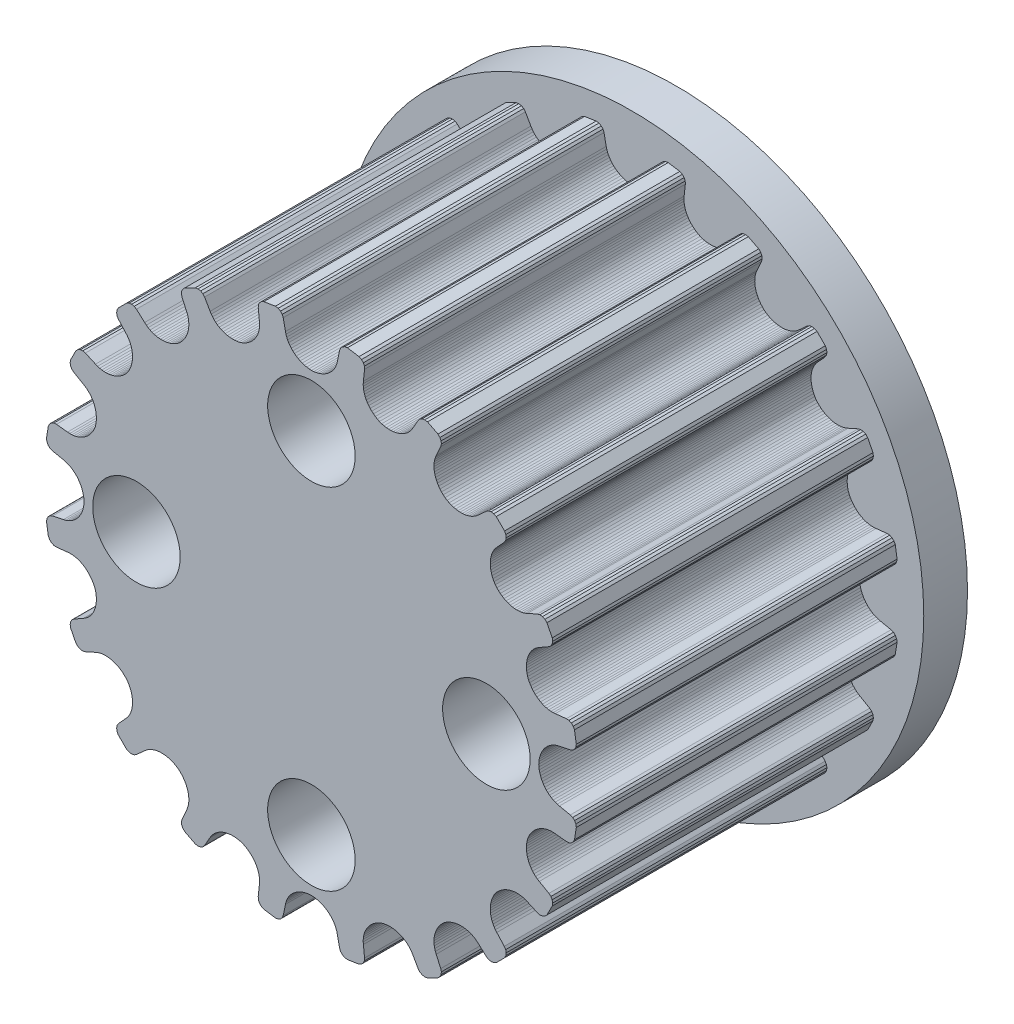
SolidWorks part; units mm, degrees
ref_plane "Front Plane" through (0, 0, 0) normal (0, 0, 1) x (1, 0, 0)
ref_plane "Top Plane" through (0, 0, 0) normal (0, 1, 0) x (1, 0, 0)
ref_plane "Right Plane" through (0, 0, 0) normal (1, 0, 0) x (0, 0, -1)
sketch "Model" plane through (0, 0, 0) normal (0, 0, 1) x (1, 0, 0)
  line L0 (-1.2351, -9.0847) -> (-1.1407, -9.0693)
  line L1 (-1.1407, -9.0693) -> (-1.0601, -9.0262)
  line L2 (-1.0601, -9.0262) -> (-1.0001, -8.9608)
  line L3 (-1.0001, -8.9608) -> (-0.9675, -8.878)
  line L4 (-0.9675, -8.878) -> (-0.8892, -8.5051)
  line L5 (-0.8892, -8.5051) -> (-0.8714, -8.4315)
  line L6 (-0.8714, -8.4315) -> (-0.847, -8.3606)
  line L7 (-0.847, -8.3606) -> (-0.8163, -8.2926)
  line L8 (-0.8163, -8.2926) -> (-0.7798, -8.2278)
  line L9 (-0.7798, -8.2278) -> (-0.7377, -8.1665)
  line L10 (-0.7377, -8.1665) -> (-0.6904, -8.109)
  line L11 (-0.6904, -8.109) -> (-0.6382, -8.0554)
  line L12 (-0.6382, -8.0554) -> (-0.5813, -8.0061)
  line L13 (-0.5813, -8.0061) -> (-0.5202, -7.9613)
  line L14 (-0.5202, -7.9613) -> (-0.4551, -7.9212)
  line L15 (-0.4551, -7.9212) -> (-0.3865, -7.8862)
  line L16 (-0.3865, -7.8862) -> (-0.3145, -7.8565)
  line L17 (-0.3145, -7.8565) -> (-0.2395, -7.8323)
  line L18 (-0.2395, -7.8323) -> (-0.162, -7.8139)
  line L19 (-0.162, -7.8139) -> (-0.0821, -7.8016)
  line L20 (-0.0821, -7.8016) -> (-0.0002, -7.7957)
  line L21 (-0.0002, -7.7957) -> (0.0817, -7.8016)
  line L22 (0.0817, -7.8016) -> (0.1616, -7.8138)
  line L23 (0.1616, -7.8138) -> (0.2392, -7.8322)
  line L24 (0.2392, -7.8322) -> (0.3142, -7.8563)
  line L25 (0.3142, -7.8563) -> (0.3861, -7.886)
  line L26 (0.3861, -7.886) -> (0.4548, -7.9211)
  line L27 (0.4548, -7.9211) -> (0.5199, -7.9611)
  line L28 (0.5199, -7.9611) -> (0.5811, -8.0059)
  line L29 (0.5811, -8.0059) -> (0.6379, -8.0553)
  line L30 (0.6379, -8.0553) -> (0.6902, -8.1089)
  line L31 (0.6902, -8.1089) -> (0.7375, -8.1665)
  line L32 (0.7375, -8.1665) -> (0.7796, -8.2278)
  line L33 (0.7796, -8.2278) -> (0.8161, -8.2926)
  line L34 (0.8161, -8.2926) -> (0.8467, -8.3606)
  line L35 (0.8467, -8.3606) -> (0.871, -8.4315)
  line L36 (0.871, -8.4315) -> (0.8888, -8.5051)
  line L37 (0.8888, -8.5051) -> (0.9668, -8.878)
  line L38 (0.9668, -8.878) -> (1, -8.9608)
  line L39 (1, -8.9608) -> (1.0602, -9.0262)
  line L40 (1.0602, -9.0262) -> (1.1407, -9.0693)
  line L41 (1.1407, -9.0693) -> (1.2351, -9.0847)
  line L42 (1.2351, -9.0847) -> (1.6327, -9.0218)
  line L43 (1.6327, -9.0218) -> (1.7177, -8.9779)
  line L44 (1.7177, -8.9779) -> (1.781, -8.912)
  line L45 (1.781, -8.912) -> (1.8178, -8.8313)
  line L46 (1.8178, -8.8313) -> (1.8233, -8.7425)
  line L47 (1.8233, -8.7425) -> (1.7825, -8.3636)
  line L48 (1.7825, -8.3636) -> (1.7768, -8.2881)
  line L49 (1.7768, -8.2881) -> (1.778, -8.2131)
  line L50 (1.778, -8.2131) -> (1.7862, -8.139)
  line L51 (1.7862, -8.139) -> (1.8009, -8.0661)
  line L52 (1.8009, -8.0661) -> (1.822, -7.9948)
  line L53 (1.822, -7.9948) -> (1.8492, -7.9254)
  line L54 (1.8492, -7.9254) -> (1.8823, -7.8583)
  line L55 (1.8823, -7.8583) -> (1.9212, -7.7939)
  line L56 (1.9212, -7.7939) -> (1.9654, -7.7324)
  line L57 (1.9654, -7.7324) -> (2.0149, -7.6742)
  line L58 (2.0149, -7.6742) -> (2.0694, -7.6196)
  line L59 (2.0694, -7.6196) -> (2.1287, -7.5691)
  line L60 (2.1287, -7.5691) -> (2.1925, -7.523)
  line L61 (2.1925, -7.523) -> (2.2606, -7.4816)
  line L62 (2.2606, -7.4816) -> (2.3328, -7.4452)
  line L63 (2.3328, -7.4452) -> (2.4088, -7.4142)
  line L64 (2.4088, -7.4142) -> (2.4885, -7.3945)
  line L65 (2.4885, -7.3945) -> (2.5683, -7.3815)
  line L66 (2.5683, -7.3815) -> (2.6478, -7.3749)
  line L67 (2.6478, -7.3749) -> (2.7265, -7.3747)
  line L68 (2.7265, -7.3747) -> (2.8042, -7.3808)
  line L69 (2.8042, -7.3808) -> (2.8803, -7.3928)
  line L70 (2.8803, -7.3928) -> (2.9546, -7.4108)
  line L71 (2.9546, -7.4108) -> (3.0266, -7.4345)
  line L72 (3.0266, -7.4345) -> (3.0959, -7.4639)
  line L73 (3.0959, -7.4639) -> (3.1622, -7.4987)
  line L74 (3.1622, -7.4987) -> (3.225, -7.5389)
  line L75 (3.225, -7.5389) -> (3.284, -7.5842)
  line L76 (3.284, -7.5842) -> (3.3387, -7.6345)
  line L77 (3.3387, -7.6345) -> (3.3888, -7.6897)
  line L78 (3.3888, -7.6897) -> (3.4339, -7.7497)
  line L79 (3.4339, -7.7497) -> (3.4736, -7.8142)
  line L80 (3.4736, -7.8142) -> (3.6629, -8.1447)
  line L81 (3.6629, -8.1447) -> (3.7201, -8.2132)
  line L82 (3.7201, -8.2132) -> (3.7975, -8.2568)
  line L83 (3.7975, -8.2568) -> (3.8875, -8.2729)
  line L84 (3.8875, -8.2729) -> (3.982, -8.2584)
  line L85 (3.982, -8.2584) -> (4.3407, -8.0757)
  line L86 (4.3407, -8.0757) -> (4.4079, -8.0077)
  line L87 (4.4079, -8.0077) -> (4.4478, -7.9255)
  line L88 (4.4478, -7.9255) -> (4.4579, -7.8373)
  line L89 (4.4579, -7.8373) -> (4.4356, -7.7512)
  line L90 (4.4356, -7.7512) -> (4.2798, -7.4035)
  line L91 (4.2798, -7.4035) -> (4.251, -7.3334)
  line L92 (4.251, -7.3334) -> (4.229, -7.2617)
  line L93 (4.229, -7.2617) -> (4.2138, -7.1887)
  line L94 (4.2138, -7.1887) -> (4.2053, -7.1148)
  line L95 (4.2053, -7.1148) -> (4.2033, -7.0405)
  line L96 (4.2033, -7.0405) -> (4.2078, -6.9661)
  line L97 (4.2078, -6.9661) -> (4.2186, -6.8921)
  line L98 (4.2186, -6.8921) -> (4.2356, -6.8187)
  line L99 (4.2356, -6.8187) -> (4.2587, -6.7466)
  line L100 (4.2587, -6.7466) -> (4.2878, -6.6759)
  line L101 (4.2878, -6.6759) -> (4.3227, -6.6072)
  line L102 (4.3227, -6.6072) -> (4.3635, -6.5409)
  line L103 (4.3635, -6.5409) -> (4.4099, -6.4773)
  line L104 (4.4099, -6.4773) -> (4.4619, -6.4168)
  line L105 (4.4619, -6.4168) -> (4.5193, -6.3599)
  line L106 (4.5193, -6.3599) -> (4.582, -6.307)
  line L107 (4.582, -6.307) -> (4.6518, -6.2636)
  line L108 (4.6518, -6.2636) -> (4.7236, -6.2265)
  line L109 (4.7236, -6.2265) -> (4.7972, -6.1958)
  line L110 (4.7972, -6.1958) -> (4.872, -6.1713)
  line L111 (4.872, -6.1713) -> (4.9477, -6.153)
  line L112 (4.9477, -6.153) -> (5.0239, -6.1409)
  line L113 (5.0239, -6.1409) -> (5.1001, -6.1351)
  line L114 (5.1001, -6.1351) -> (5.1759, -6.1354)
  line L115 (5.1759, -6.1354) -> (5.2509, -6.1419)
  line L116 (5.2509, -6.1419) -> (5.3247, -6.1545)
  line L117 (5.3247, -6.1545) -> (5.3968, -6.1733)
  line L118 (5.3968, -6.1733) -> (5.4669, -6.1982)
  line L119 (5.4669, -6.1982) -> (5.5345, -6.2291)
  line L120 (5.5345, -6.2291) -> (5.5992, -6.2662)
  line L121 (5.5992, -6.2662) -> (5.6606, -6.3092)
  line L122 (5.6606, -6.3092) -> (5.7183, -6.3583)
  line L123 (5.7183, -6.3583) -> (6.0005, -6.6142)
  line L124 (6.0005, -6.6142) -> (6.076, -6.6616)
  line L125 (6.076, -6.6616) -> (6.1632, -6.6792)
  line L126 (6.1632, -6.6792) -> (6.2536, -6.6667)
  line L127 (6.2536, -6.6667) -> (6.3391, -6.6238)
  line L128 (6.3391, -6.6238) -> (6.6238, -6.3391)
  line L129 (6.6238, -6.3391) -> (6.6667, -6.2536)
  line L130 (6.6667, -6.2536) -> (6.6792, -6.1631)
  line L131 (6.6792, -6.1631) -> (6.6615, -6.0761)
  line L132 (6.6615, -6.0761) -> (6.6138, -6.0011)
  line L133 (6.6138, -6.0011) -> (6.3581, -5.7186)
  line L134 (6.3581, -5.7186) -> (6.3091, -5.6609)
  line L135 (6.3091, -5.6609) -> (6.266, -5.5994)
  line L136 (6.266, -5.5994) -> (6.229, -5.5347)
  line L137 (6.229, -5.5347) -> (6.1981, -5.4671)
  line L138 (6.1981, -5.4671) -> (6.1732, -5.397)
  line L139 (6.1732, -5.397) -> (6.1545, -5.3249)
  line L140 (6.1545, -5.3249) -> (6.1419, -5.2511)
  line L141 (6.1419, -5.2511) -> (6.1354, -5.1761)
  line L142 (6.1354, -5.1761) -> (6.135, -5.1004)
  line L143 (6.135, -5.1004) -> (6.1409, -5.0242)
  line L144 (6.1409, -5.0242) -> (6.1529, -4.948)
  line L145 (6.1529, -4.948) -> (6.1712, -4.8723)
  line L146 (6.1712, -4.8723) -> (6.1957, -4.7975)
  line L147 (6.1957, -4.7975) -> (6.2264, -4.724)
  line L148 (6.2264, -4.724) -> (6.2634, -4.6521)
  line L149 (6.2634, -4.6521) -> (6.3067, -4.5823)
  line L150 (6.3067, -4.5823) -> (6.3596, -4.5196)
  line L151 (6.3596, -4.5196) -> (6.4165, -4.4621)
  line L152 (6.4165, -4.4621) -> (6.477, -4.4101)
  line L153 (6.477, -4.4101) -> (6.5406, -4.3637)
  line L154 (6.5406, -4.3637) -> (6.6069, -4.3229)
  line L155 (6.6069, -4.3229) -> (6.6756, -4.2879)
  line L156 (6.6756, -4.2879) -> (6.7463, -4.2588)
  line L157 (6.7463, -4.2588) -> (6.8185, -4.2357)
  line L158 (6.8185, -4.2357) -> (6.8918, -4.2187)
  line L159 (6.8918, -4.2187) -> (6.9659, -4.2079)
  line L160 (6.9659, -4.2079) -> (7.0403, -4.2035)
  line L161 (7.0403, -4.2035) -> (7.1147, -4.2055)
  line L162 (7.1147, -4.2055) -> (7.1885, -4.214)
  line L163 (7.1885, -4.214) -> (7.2615, -4.2292)
  line L164 (7.2615, -4.2292) -> (7.3332, -4.2512)
  line L165 (7.3332, -4.2512) -> (7.4032, -4.2801)
  line L166 (7.4032, -4.2801) -> (7.7507, -4.4362)
  line L167 (7.7507, -4.4362) -> (7.8372, -4.458)
  line L168 (7.8372, -4.458) -> (7.9255, -4.4478)
  line L169 (7.9255, -4.4478) -> (8.0077, -4.4079)
  line L170 (8.0077, -4.4079) -> (8.0757, -4.3407)
  line L171 (8.0757, -4.3407) -> (8.2584, -3.982)
  line L172 (8.2584, -3.982) -> (8.2729, -3.8874)
  line L173 (8.2729, -3.8874) -> (8.2568, -3.7975)
  line L174 (8.2568, -3.7975) -> (8.2131, -3.7202)
  line L175 (8.2131, -3.7202) -> (8.1445, -3.6636)
  line L176 (8.1445, -3.6636) -> (7.8141, -3.4739)
  line L177 (7.8141, -3.4739) -> (7.7496, -3.4342)
  line L178 (7.7496, -3.4342) -> (7.6897, -3.3891)
  line L179 (7.6897, -3.3891) -> (7.6345, -3.3389)
  line L180 (7.6345, -3.3389) -> (7.5842, -3.2842)
  line L181 (7.5842, -3.2842) -> (7.5389, -3.2252)
  line L182 (7.5389, -3.2252) -> (7.4987, -3.1624)
  line L183 (7.4987, -3.1624) -> (7.4639, -3.0962)
  line L184 (7.4639, -3.0962) -> (7.4346, -3.0269)
  line L185 (7.4346, -3.0269) -> (7.4109, -2.9549)
  line L186 (7.4109, -2.9549) -> (7.3929, -2.8806)
  line L187 (7.3929, -2.8806) -> (7.3808, -2.8045)
  line L188 (7.3808, -2.8045) -> (7.3748, -2.7269)
  line L189 (7.3748, -2.7269) -> (7.3749, -2.6481)
  line L190 (7.3749, -2.6481) -> (7.3815, -2.5687)
  line L191 (7.3815, -2.5687) -> (7.3944, -2.4889)
  line L192 (7.3944, -2.4889) -> (7.4141, -2.4092)
  line L193 (7.4141, -2.4092) -> (7.445, -2.3331)
  line L194 (7.445, -2.3331) -> (7.4813, -2.2609)
  line L195 (7.4813, -2.2609) -> (7.5228, -2.1928)
  line L196 (7.5228, -2.1928) -> (7.5689, -2.129)
  line L197 (7.5689, -2.129) -> (7.6194, -2.0697)
  line L198 (7.6194, -2.0697) -> (7.6739, -2.0152)
  line L199 (7.6739, -2.0152) -> (7.7321, -1.9656)
  line L200 (7.7321, -1.9656) -> (7.7937, -1.9213)
  line L201 (7.7937, -1.9213) -> (7.8582, -1.8825)
  line L202 (7.8582, -1.8825) -> (7.9253, -1.8494)
  line L203 (7.9253, -1.8494) -> (7.9947, -1.8221)
  line L204 (7.9947, -1.8221) -> (8.066, -1.8011)
  line L205 (8.066, -1.8011) -> (8.1389, -1.7864)
  line L206 (8.1389, -1.7864) -> (8.213, -1.7783)
  line L207 (8.213, -1.7783) -> (8.288, -1.7771)
  line L208 (8.288, -1.7771) -> (8.3635, -1.7829)
  line L209 (8.3635, -1.7829) -> (8.7422, -1.824)
  line L210 (8.7422, -1.824) -> (8.8312, -1.818)
  line L211 (8.8312, -1.818) -> (8.9121, -1.781)
  line L212 (8.9121, -1.781) -> (8.9779, -1.7177)
  line L213 (8.9779, -1.7177) -> (9.0218, -1.6327)
  line L214 (9.0218, -1.6327) -> (9.0847, -1.2351)
  line L215 (9.0847, -1.2351) -> (9.0693, -1.1407)
  line L216 (9.0693, -1.1407) -> (9.0262, -1.0601)
  line L217 (9.0262, -1.0601) -> (8.9608, -1.0001)
  line L218 (8.9608, -1.0001) -> (8.878, -0.9675)
  line L219 (8.878, -0.9675) -> (8.5051, -0.8892)
  line L220 (8.5051, -0.8892) -> (8.4315, -0.8714)
  line L221 (8.4315, -0.8714) -> (8.3606, -0.847)
  line L222 (8.3606, -0.847) -> (8.2926, -0.8163)
  line L223 (8.2926, -0.8163) -> (8.2278, -0.7798)
  line L224 (8.2278, -0.7798) -> (8.1665, -0.7377)
  line L225 (8.1665, -0.7377) -> (8.109, -0.6904)
  line L226 (8.109, -0.6904) -> (8.0554, -0.6382)
  line L227 (8.0554, -0.6382) -> (8.0061, -0.5813)
  line L228 (8.0061, -0.5813) -> (7.9613, -0.5202)
  line L229 (7.9613, -0.5202) -> (7.9212, -0.4551)
  line L230 (7.9212, -0.4551) -> (7.8862, -0.3865)
  line L231 (7.8862, -0.3865) -> (7.8565, -0.3145)
  line L232 (7.8565, -0.3145) -> (7.8323, -0.2395)
  line L233 (7.8323, -0.2395) -> (7.8139, -0.162)
  line L234 (7.8139, -0.162) -> (7.8016, -0.0821)
  line L235 (7.8016, -0.0821) -> (7.7957, -0.0002)
  line L236 (7.7957, -0.0002) -> (7.8016, 0.0817)
  line L237 (7.8016, 0.0817) -> (7.8138, 0.1616)
  line L238 (7.8138, 0.1616) -> (7.8322, 0.2392)
  line L239 (7.8322, 0.2392) -> (7.8563, 0.3142)
  line L240 (7.8563, 0.3142) -> (7.886, 0.3861)
  line L241 (7.886, 0.3861) -> (7.9211, 0.4548)
  line L242 (7.9211, 0.4548) -> (7.9611, 0.5199)
  line L243 (7.9611, 0.5199) -> (8.0059, 0.5811)
  line L244 (8.0059, 0.5811) -> (8.0553, 0.6379)
  line L245 (8.0553, 0.6379) -> (8.1089, 0.6902)
  line L246 (8.1089, 0.6902) -> (8.1665, 0.7375)
  line L247 (8.1665, 0.7375) -> (8.2278, 0.7796)
  line L248 (8.2278, 0.7796) -> (8.2926, 0.8161)
  line L249 (8.2926, 0.8161) -> (8.3606, 0.8467)
  line L250 (8.3606, 0.8467) -> (8.4315, 0.871)
  line L251 (8.4315, 0.871) -> (8.5051, 0.8888)
  line L252 (8.5051, 0.8888) -> (8.878, 0.9668)
  line L253 (8.878, 0.9668) -> (8.9608, 1)
  line L254 (8.9608, 1) -> (9.0262, 1.0602)
  line L255 (9.0262, 1.0602) -> (9.0693, 1.1407)
  line L256 (9.0693, 1.1407) -> (9.0847, 1.2351)
  line L257 (9.0847, 1.2351) -> (9.0218, 1.6327)
  line L258 (9.0218, 1.6327) -> (8.9779, 1.7177)
  line L259 (8.9779, 1.7177) -> (8.912, 1.781)
  line L260 (8.912, 1.781) -> (8.8313, 1.8178)
  line L261 (8.8313, 1.8178) -> (8.7425, 1.8233)
  line L262 (8.7425, 1.8233) -> (8.3636, 1.7825)
  line L263 (8.3636, 1.7825) -> (8.2881, 1.7768)
  line L264 (8.2881, 1.7768) -> (8.2131, 1.778)
  line L265 (8.2131, 1.778) -> (8.139, 1.7862)
  line L266 (8.139, 1.7862) -> (8.0661, 1.8009)
  line L267 (8.0661, 1.8009) -> (7.9948, 1.822)
  line L268 (7.9948, 1.822) -> (7.9254, 1.8492)
  line L269 (7.9254, 1.8492) -> (7.8583, 1.8823)
  line L270 (7.8583, 1.8823) -> (7.7939, 1.9212)
  line L271 (7.7939, 1.9212) -> (7.7324, 1.9654)
  line L272 (7.7324, 1.9654) -> (7.6742, 2.0149)
  line L273 (7.6742, 2.0149) -> (7.6196, 2.0694)
  line L274 (7.6196, 2.0694) -> (7.5691, 2.1287)
  line L275 (7.5691, 2.1287) -> (7.523, 2.1925)
  line L276 (7.523, 2.1925) -> (7.4816, 2.2606)
  line L277 (7.4816, 2.2606) -> (7.4452, 2.3328)
  line L278 (7.4452, 2.3328) -> (7.4142, 2.4088)
  line L279 (7.4142, 2.4088) -> (7.3945, 2.4885)
  line L280 (7.3945, 2.4885) -> (7.3815, 2.5683)
  line L281 (7.3815, 2.5683) -> (7.3749, 2.6478)
  line L282 (7.3749, 2.6478) -> (7.3747, 2.7265)
  line L283 (7.3747, 2.7265) -> (7.3808, 2.8042)
  line L284 (7.3808, 2.8042) -> (7.3928, 2.8803)
  line L285 (7.3928, 2.8803) -> (7.4108, 2.9546)
  line L286 (7.4108, 2.9546) -> (7.4345, 3.0266)
  line L287 (7.4345, 3.0266) -> (7.4639, 3.0959)
  line L288 (7.4639, 3.0959) -> (7.4987, 3.1622)
  line L289 (7.4987, 3.1622) -> (7.5389, 3.225)
  line L290 (7.5389, 3.225) -> (7.5842, 3.284)
  line L291 (7.5842, 3.284) -> (7.6345, 3.3387)
  line L292 (7.6345, 3.3387) -> (7.6897, 3.3888)
  line L293 (7.6897, 3.3888) -> (7.7497, 3.4339)
  line L294 (7.7497, 3.4339) -> (7.8142, 3.4736)
  line L295 (7.8142, 3.4736) -> (8.1447, 3.6629)
  line L296 (8.1447, 3.6629) -> (8.2132, 3.7201)
  line L297 (8.2132, 3.7201) -> (8.2568, 3.7975)
  line L298 (8.2568, 3.7975) -> (8.2729, 3.8875)
  line L299 (8.2729, 3.8875) -> (8.2584, 3.982)
  line L300 (8.2584, 3.982) -> (8.0757, 4.3407)
  line L301 (8.0757, 4.3407) -> (8.0077, 4.4079)
  line L302 (8.0077, 4.4079) -> (7.9255, 4.4478)
  line L303 (7.9255, 4.4478) -> (7.8373, 4.4579)
  line L304 (7.8373, 4.4579) -> (7.7512, 4.4356)
  line L305 (7.7512, 4.4356) -> (7.4035, 4.2798)
  line L306 (7.4035, 4.2798) -> (7.3334, 4.251)
  line L307 (7.3334, 4.251) -> (7.2617, 4.229)
  line L308 (7.2617, 4.229) -> (7.1887, 4.2138)
  line L309 (7.1887, 4.2138) -> (7.1148, 4.2053)
  line L310 (7.1148, 4.2053) -> (7.0405, 4.2033)
  line L311 (7.0405, 4.2033) -> (6.9661, 4.2078)
  line L312 (6.9661, 4.2078) -> (6.8921, 4.2186)
  line L313 (6.8921, 4.2186) -> (6.8187, 4.2356)
  line L314 (6.8187, 4.2356) -> (6.7466, 4.2587)
  line L315 (6.7466, 4.2587) -> (6.6759, 4.2878)
  line L316 (6.6759, 4.2878) -> (6.6072, 4.3227)
  line L317 (6.6072, 4.3227) -> (6.5409, 4.3635)
  line L318 (6.5409, 4.3635) -> (6.4773, 4.4099)
  line L319 (6.4773, 4.4099) -> (6.4168, 4.4619)
  line L320 (6.4168, 4.4619) -> (6.3599, 4.5193)
  line L321 (6.3599, 4.5193) -> (6.307, 4.582)
  line L322 (6.307, 4.582) -> (6.2636, 4.6518)
  line L323 (6.2636, 4.6518) -> (6.2265, 4.7236)
  line L324 (6.2265, 4.7236) -> (6.1958, 4.7972)
  line L325 (6.1958, 4.7972) -> (6.1713, 4.872)
  line L326 (6.1713, 4.872) -> (6.153, 4.9477)
  line L327 (6.153, 4.9477) -> (6.1409, 5.0239)
  line L328 (6.1409, 5.0239) -> (6.1351, 5.1001)
  line L329 (6.1351, 5.1001) -> (6.1354, 5.1759)
  line L330 (6.1354, 5.1759) -> (6.1419, 5.2509)
  line L331 (6.1419, 5.2509) -> (6.1545, 5.3247)
  line L332 (6.1545, 5.3247) -> (6.1733, 5.3968)
  line L333 (6.1733, 5.3968) -> (6.1982, 5.4669)
  line L334 (6.1982, 5.4669) -> (6.2291, 5.5345)
  line L335 (6.2291, 5.5345) -> (6.2662, 5.5992)
  line L336 (6.2662, 5.5992) -> (6.3092, 5.6606)
  line L337 (6.3092, 5.6606) -> (6.3583, 5.7183)
  line L338 (6.3583, 5.7183) -> (6.6142, 6.0005)
  line L339 (6.6142, 6.0005) -> (6.6616, 6.076)
  line L340 (6.6616, 6.076) -> (6.6792, 6.1632)
  line L341 (6.6792, 6.1632) -> (6.6667, 6.2536)
  line L342 (6.6667, 6.2536) -> (6.6238, 6.3391)
  line L343 (6.6238, 6.3391) -> (6.3391, 6.6238)
  line L344 (6.3391, 6.6238) -> (6.2536, 6.6667)
  line L345 (6.2536, 6.6667) -> (6.1631, 6.6792)
  line L346 (6.1631, 6.6792) -> (6.0761, 6.6615)
  line L347 (6.0761, 6.6615) -> (6.0011, 6.6138)
  line L348 (6.0011, 6.6138) -> (5.7186, 6.3581)
  line L349 (5.7186, 6.3581) -> (5.6609, 6.3091)
  line L350 (5.6609, 6.3091) -> (5.5994, 6.266)
  line L351 (5.5994, 6.266) -> (5.5347, 6.229)
  line L352 (5.5347, 6.229) -> (5.4671, 6.1981)
  line L353 (5.4671, 6.1981) -> (5.397, 6.1732)
  line L354 (5.397, 6.1732) -> (5.3249, 6.1545)
  line L355 (5.3249, 6.1545) -> (5.2511, 6.1419)
  line L356 (5.2511, 6.1419) -> (5.1761, 6.1354)
  line L357 (5.1761, 6.1354) -> (5.1004, 6.135)
  line L358 (5.1004, 6.135) -> (5.0242, 6.1409)
  line L359 (5.0242, 6.1409) -> (4.948, 6.1529)
  line L360 (4.948, 6.1529) -> (4.8723, 6.1712)
  line L361 (4.8723, 6.1712) -> (4.7975, 6.1957)
  line L362 (4.7975, 6.1957) -> (4.724, 6.2264)
  line L363 (4.724, 6.2264) -> (4.6521, 6.2634)
  line L364 (4.6521, 6.2634) -> (4.5823, 6.3067)
  line L365 (4.5823, 6.3067) -> (4.5196, 6.3596)
  line L366 (4.5196, 6.3596) -> (4.4621, 6.4165)
  line L367 (4.4621, 6.4165) -> (4.4101, 6.477)
  line L368 (4.4101, 6.477) -> (4.3637, 6.5406)
  line L369 (4.3637, 6.5406) -> (4.3229, 6.6069)
  line L370 (4.3229, 6.6069) -> (4.2879, 6.6756)
  line L371 (4.2879, 6.6756) -> (4.2588, 6.7463)
  line L372 (4.2588, 6.7463) -> (4.2357, 6.8185)
  line L373 (4.2357, 6.8185) -> (4.2187, 6.8918)
  line L374 (4.2187, 6.8918) -> (4.2079, 6.9659)
  line L375 (4.2079, 6.9659) -> (4.2035, 7.0403)
  line L376 (4.2035, 7.0403) -> (4.2055, 7.1147)
  line L377 (4.2055, 7.1147) -> (4.214, 7.1885)
  line L378 (4.214, 7.1885) -> (4.2292, 7.2615)
  line L379 (4.2292, 7.2615) -> (4.2512, 7.3332)
  line L380 (4.2512, 7.3332) -> (4.2801, 7.4032)
  line L381 (4.2801, 7.4032) -> (4.4362, 7.7507)
  line L382 (4.4362, 7.7507) -> (4.458, 7.8372)
  line L383 (4.458, 7.8372) -> (4.4478, 7.9255)
  line L384 (4.4478, 7.9255) -> (4.4079, 8.0077)
  line L385 (4.4079, 8.0077) -> (4.3407, 8.0757)
  line L386 (4.3407, 8.0757) -> (3.982, 8.2584)
  line L387 (3.982, 8.2584) -> (3.8874, 8.2729)
  line L388 (3.8874, 8.2729) -> (3.7975, 8.2568)
  line L389 (3.7975, 8.2568) -> (3.7202, 8.2131)
  line L390 (3.7202, 8.2131) -> (3.6636, 8.1445)
  line L391 (3.6636, 8.1445) -> (3.4739, 7.8141)
  line L392 (3.4739, 7.8141) -> (3.4342, 7.7496)
  line L393 (3.4342, 7.7496) -> (3.3891, 7.6897)
  line L394 (3.3891, 7.6897) -> (3.3389, 7.6345)
  line L395 (3.3389, 7.6345) -> (3.2842, 7.5842)
  line L396 (3.2842, 7.5842) -> (3.2252, 7.5389)
  line L397 (3.2252, 7.5389) -> (3.1624, 7.4987)
  line L398 (3.1624, 7.4987) -> (3.0962, 7.4639)
  line L399 (3.0962, 7.4639) -> (3.0269, 7.4346)
  line L400 (3.0269, 7.4346) -> (2.9549, 7.4109)
  line L401 (2.9549, 7.4109) -> (2.8806, 7.3929)
  line L402 (2.8806, 7.3929) -> (2.8045, 7.3808)
  line L403 (2.8045, 7.3808) -> (2.7269, 7.3748)
  line L404 (2.7269, 7.3748) -> (2.6481, 7.3749)
  line L405 (2.6481, 7.3749) -> (2.5687, 7.3815)
  line L406 (2.5687, 7.3815) -> (2.4889, 7.3944)
  line L407 (2.4889, 7.3944) -> (2.4092, 7.4141)
  line L408 (2.4092, 7.4141) -> (2.3331, 7.445)
  line L409 (2.3331, 7.445) -> (2.2609, 7.4813)
  line L410 (2.2609, 7.4813) -> (2.1928, 7.5228)
  line L411 (2.1928, 7.5228) -> (2.129, 7.5689)
  line L412 (2.129, 7.5689) -> (2.0697, 7.6194)
  line L413 (2.0697, 7.6194) -> (2.0152, 7.6739)
  line L414 (2.0152, 7.6739) -> (1.9656, 7.7321)
  line L415 (1.9656, 7.7321) -> (1.9213, 7.7937)
  line L416 (1.9213, 7.7937) -> (1.8825, 7.8582)
  line L417 (1.8825, 7.8582) -> (1.8494, 7.9253)
  line L418 (1.8494, 7.9253) -> (1.8221, 7.9947)
  line L419 (1.8221, 7.9947) -> (1.8011, 8.066)
  line L420 (1.8011, 8.066) -> (1.7864, 8.1389)
  line L421 (1.7864, 8.1389) -> (1.7783, 8.213)
  line L422 (1.7783, 8.213) -> (1.7771, 8.288)
  line L423 (1.7771, 8.288) -> (1.7829, 8.3635)
  line L424 (1.7829, 8.3635) -> (1.824, 8.7422)
  line L425 (1.824, 8.7422) -> (1.818, 8.8312)
  line L426 (1.818, 8.8312) -> (1.781, 8.9121)
  line L427 (1.781, 8.9121) -> (1.7177, 8.9779)
  line L428 (1.7177, 8.9779) -> (1.6327, 9.0218)
  line L429 (1.6327, 9.0218) -> (1.2351, 9.0847)
  line L430 (1.2351, 9.0847) -> (1.1407, 9.0693)
  line L431 (1.1407, 9.0693) -> (1.0601, 9.0262)
  line L432 (1.0601, 9.0262) -> (1.0001, 8.9608)
  line L433 (1.0001, 8.9608) -> (0.9675, 8.878)
  line L434 (0.9675, 8.878) -> (0.8892, 8.5051)
  line L435 (0.8892, 8.5051) -> (0.8714, 8.4315)
  line L436 (0.8714, 8.4315) -> (0.847, 8.3606)
  line L437 (0.847, 8.3606) -> (0.8163, 8.2926)
  line L438 (0.8163, 8.2926) -> (0.7798, 8.2278)
  line L439 (0.7798, 8.2278) -> (0.7377, 8.1665)
  line L440 (0.7377, 8.1665) -> (0.6904, 8.109)
  line L441 (0.6904, 8.109) -> (0.6382, 8.0554)
  line L442 (0.6382, 8.0554) -> (0.5813, 8.0061)
  line L443 (0.5813, 8.0061) -> (0.5202, 7.9613)
  line L444 (0.5202, 7.9613) -> (0.4551, 7.9212)
  line L445 (0.4551, 7.9212) -> (0.3865, 7.8862)
  line L446 (0.3865, 7.8862) -> (0.3145, 7.8565)
  line L447 (0.3145, 7.8565) -> (0.2395, 7.8323)
  line L448 (0.2395, 7.8323) -> (0.162, 7.8139)
  line L449 (0.162, 7.8139) -> (0.0821, 7.8016)
  line L450 (0.0821, 7.8016) -> (0.0002, 7.7957)
  line L451 (0.0002, 7.7957) -> (-0.0817, 7.8016)
  line L452 (-0.0817, 7.8016) -> (-0.1616, 7.8138)
  line L453 (-0.1616, 7.8138) -> (-0.2392, 7.8322)
  line L454 (-0.2392, 7.8322) -> (-0.3142, 7.8563)
  line L455 (-0.3142, 7.8563) -> (-0.3861, 7.886)
  line L456 (-0.3861, 7.886) -> (-0.4548, 7.9211)
  line L457 (-0.4548, 7.9211) -> (-0.5199, 7.9611)
  line L458 (-0.5199, 7.9611) -> (-0.5811, 8.0059)
  line L459 (-0.5811, 8.0059) -> (-0.6379, 8.0553)
  line L460 (-0.6379, 8.0553) -> (-0.6902, 8.1089)
  line L461 (-0.6902, 8.1089) -> (-0.7375, 8.1665)
  line L462 (-0.7375, 8.1665) -> (-0.7796, 8.2278)
  line L463 (-0.7796, 8.2278) -> (-0.8161, 8.2926)
  line L464 (-0.8161, 8.2926) -> (-0.8467, 8.3606)
  line L465 (-0.8467, 8.3606) -> (-0.871, 8.4315)
  line L466 (-0.871, 8.4315) -> (-0.8888, 8.5051)
  line L467 (-0.8888, 8.5051) -> (-0.9668, 8.878)
  line L468 (-0.9668, 8.878) -> (-1, 8.9608)
  line L469 (-1, 8.9608) -> (-1.0602, 9.0262)
  line L470 (-1.0602, 9.0262) -> (-1.1407, 9.0693)
  line L471 (-1.1407, 9.0693) -> (-1.2351, 9.0847)
  line L472 (-1.2351, 9.0847) -> (-1.6327, 9.0218)
  line L473 (-1.6327, 9.0218) -> (-1.7177, 8.9779)
  line L474 (-1.7177, 8.9779) -> (-1.781, 8.912)
  line L475 (-1.781, 8.912) -> (-1.8178, 8.8313)
  line L476 (-1.8178, 8.8313) -> (-1.8233, 8.7425)
  line L477 (-1.8233, 8.7425) -> (-1.7825, 8.3636)
  line L478 (-1.7825, 8.3636) -> (-1.7768, 8.2881)
  line L479 (-1.7768, 8.2881) -> (-1.778, 8.2131)
  line L480 (-1.778, 8.2131) -> (-1.7862, 8.139)
  line L481 (-1.7862, 8.139) -> (-1.8009, 8.0661)
  line L482 (-1.8009, 8.0661) -> (-1.822, 7.9948)
  line L483 (-1.822, 7.9948) -> (-1.8492, 7.9254)
  line L484 (-1.8492, 7.9254) -> (-1.8823, 7.8583)
  line L485 (-1.8823, 7.8583) -> (-1.9212, 7.7939)
  line L486 (-1.9212, 7.7939) -> (-1.9654, 7.7324)
  line L487 (-1.9654, 7.7324) -> (-2.0149, 7.6742)
  line L488 (-2.0149, 7.6742) -> (-2.0694, 7.6196)
  line L489 (-2.0694, 7.6196) -> (-2.1287, 7.5691)
  line L490 (-2.1287, 7.5691) -> (-2.1925, 7.523)
  line L491 (-2.1925, 7.523) -> (-2.2606, 7.4816)
  line L492 (-2.2606, 7.4816) -> (-2.3328, 7.4452)
  line L493 (-2.3328, 7.4452) -> (-2.4088, 7.4142)
  line L494 (-2.4088, 7.4142) -> (-2.4885, 7.3945)
  line L495 (-2.4885, 7.3945) -> (-2.5683, 7.3815)
  line L496 (-2.5683, 7.3815) -> (-2.6478, 7.3749)
  line L497 (-2.6478, 7.3749) -> (-2.7265, 7.3747)
  line L498 (-2.7265, 7.3747) -> (-2.8042, 7.3808)
  line L499 (-2.8042, 7.3808) -> (-2.8803, 7.3928)
  line L500 (-2.8803, 7.3928) -> (-2.9546, 7.4108)
  line L501 (-2.9546, 7.4108) -> (-3.0266, 7.4345)
  line L502 (-3.0266, 7.4345) -> (-3.0959, 7.4639)
  line L503 (-3.0959, 7.4639) -> (-3.1622, 7.4987)
  line L504 (-3.1622, 7.4987) -> (-3.225, 7.5389)
  line L505 (-3.225, 7.5389) -> (-3.284, 7.5842)
  line L506 (-3.284, 7.5842) -> (-3.3387, 7.6345)
  line L507 (-3.3387, 7.6345) -> (-3.3888, 7.6897)
  line L508 (-3.3888, 7.6897) -> (-3.4339, 7.7497)
  line L509 (-3.4339, 7.7497) -> (-3.4736, 7.8142)
  line L510 (-3.4736, 7.8142) -> (-3.6629, 8.1447)
  line L511 (-3.6629, 8.1447) -> (-3.7201, 8.2132)
  line L512 (-3.7201, 8.2132) -> (-3.7975, 8.2568)
  line L513 (-3.7975, 8.2568) -> (-3.8875, 8.2729)
  line L514 (-3.8875, 8.2729) -> (-3.982, 8.2584)
  line L515 (-3.982, 8.2584) -> (-4.3407, 8.0757)
  line L516 (-4.3407, 8.0757) -> (-4.4079, 8.0077)
  line L517 (-4.4079, 8.0077) -> (-4.4478, 7.9255)
  line L518 (-4.4478, 7.9255) -> (-4.4579, 7.8373)
  line L519 (-4.4579, 7.8373) -> (-4.4356, 7.7512)
  line L520 (-4.4356, 7.7512) -> (-4.2798, 7.4035)
  line L521 (-4.2798, 7.4035) -> (-4.251, 7.3334)
  line L522 (-4.251, 7.3334) -> (-4.229, 7.2617)
  line L523 (-4.229, 7.2617) -> (-4.2138, 7.1887)
  line L524 (-4.2138, 7.1887) -> (-4.2053, 7.1148)
  line L525 (-4.2053, 7.1148) -> (-4.2033, 7.0405)
  line L526 (-4.2033, 7.0405) -> (-4.2078, 6.9661)
  line L527 (-4.2078, 6.9661) -> (-4.2186, 6.8921)
  line L528 (-4.2186, 6.8921) -> (-4.2356, 6.8187)
  line L529 (-4.2356, 6.8187) -> (-4.2587, 6.7466)
  line L530 (-4.2587, 6.7466) -> (-4.2878, 6.6759)
  line L531 (-4.2878, 6.6759) -> (-4.3227, 6.6072)
  line L532 (-4.3227, 6.6072) -> (-4.3635, 6.5409)
  line L533 (-4.3635, 6.5409) -> (-4.4099, 6.4773)
  line L534 (-4.4099, 6.4773) -> (-4.4619, 6.4168)
  line L535 (-4.4619, 6.4168) -> (-4.5193, 6.3599)
  line L536 (-4.5193, 6.3599) -> (-4.582, 6.307)
  line L537 (-4.582, 6.307) -> (-4.6518, 6.2636)
  line L538 (-4.6518, 6.2636) -> (-4.7236, 6.2265)
  line L539 (-4.7236, 6.2265) -> (-4.7972, 6.1958)
  line L540 (-4.7972, 6.1958) -> (-4.872, 6.1713)
  line L541 (-4.872, 6.1713) -> (-4.9477, 6.153)
  line L542 (-4.9477, 6.153) -> (-5.0239, 6.1409)
  line L543 (-5.0239, 6.1409) -> (-5.1001, 6.1351)
  line L544 (-5.1001, 6.1351) -> (-5.1759, 6.1354)
  line L545 (-5.1759, 6.1354) -> (-5.2509, 6.1419)
  line L546 (-5.2509, 6.1419) -> (-5.3247, 6.1545)
  line L547 (-5.3247, 6.1545) -> (-5.3968, 6.1733)
  line L548 (-5.3968, 6.1733) -> (-5.4669, 6.1982)
  line L549 (-5.4669, 6.1982) -> (-5.5345, 6.2291)
  line L550 (-5.5345, 6.2291) -> (-5.5992, 6.2662)
  line L551 (-5.5992, 6.2662) -> (-5.6606, 6.3092)
  line L552 (-5.6606, 6.3092) -> (-5.7183, 6.3583)
  line L553 (-5.7183, 6.3583) -> (-6.0005, 6.6142)
  line L554 (-6.0005, 6.6142) -> (-6.076, 6.6616)
  line L555 (-6.076, 6.6616) -> (-6.1632, 6.6792)
  line L556 (-6.1632, 6.6792) -> (-6.2536, 6.6667)
  line L557 (-6.2536, 6.6667) -> (-6.3391, 6.6238)
  line L558 (-6.3391, 6.6238) -> (-6.6238, 6.3391)
  line L559 (-6.6238, 6.3391) -> (-6.6667, 6.2536)
  line L560 (-6.6667, 6.2536) -> (-6.6792, 6.1631)
  line L561 (-6.6792, 6.1631) -> (-6.6615, 6.0761)
  line L562 (-6.6615, 6.0761) -> (-6.6138, 6.0011)
  line L563 (-6.6138, 6.0011) -> (-6.3581, 5.7186)
  line L564 (-6.3581, 5.7186) -> (-6.3091, 5.6609)
  line L565 (-6.3091, 5.6609) -> (-6.266, 5.5994)
  line L566 (-6.266, 5.5994) -> (-6.229, 5.5347)
  line L567 (-6.229, 5.5347) -> (-6.1981, 5.4671)
  line L568 (-6.1981, 5.4671) -> (-6.1732, 5.397)
  line L569 (-6.1732, 5.397) -> (-6.1545, 5.3249)
  line L570 (-6.1545, 5.3249) -> (-6.1419, 5.2511)
  line L571 (-6.1419, 5.2511) -> (-6.1354, 5.1761)
  line L572 (-6.1354, 5.1761) -> (-6.135, 5.1004)
  line L573 (-6.135, 5.1004) -> (-6.1409, 5.0242)
  line L574 (-6.1409, 5.0242) -> (-6.1529, 4.948)
  line L575 (-6.1529, 4.948) -> (-6.1712, 4.8723)
  line L576 (-6.1712, 4.8723) -> (-6.1957, 4.7975)
  line L577 (-6.1957, 4.7975) -> (-6.2264, 4.724)
  line L578 (-6.2264, 4.724) -> (-6.2634, 4.6521)
  line L579 (-6.2634, 4.6521) -> (-6.3067, 4.5823)
  line L580 (-6.3067, 4.5823) -> (-6.3596, 4.5196)
  line L581 (-6.3596, 4.5196) -> (-6.4165, 4.4621)
  line L582 (-6.4165, 4.4621) -> (-6.477, 4.4101)
  line L583 (-6.477, 4.4101) -> (-6.5406, 4.3637)
  line L584 (-6.5406, 4.3637) -> (-6.6069, 4.3229)
  line L585 (-6.6069, 4.3229) -> (-6.6756, 4.2879)
  line L586 (-6.6756, 4.2879) -> (-6.7463, 4.2588)
  line L587 (-6.7463, 4.2588) -> (-6.8185, 4.2357)
  line L588 (-6.8185, 4.2357) -> (-6.8918, 4.2187)
  line L589 (-6.8918, 4.2187) -> (-6.9659, 4.2079)
  line L590 (-6.9659, 4.2079) -> (-7.0403, 4.2035)
  line L591 (-7.0403, 4.2035) -> (-7.1147, 4.2055)
  line L592 (-7.1147, 4.2055) -> (-7.1885, 4.214)
  line L593 (-7.1885, 4.214) -> (-7.2615, 4.2292)
  line L594 (-7.2615, 4.2292) -> (-7.3332, 4.2512)
  line L595 (-7.3332, 4.2512) -> (-7.4032, 4.2801)
  line L596 (-7.4032, 4.2801) -> (-7.7507, 4.4362)
  line L597 (-7.7507, 4.4362) -> (-7.8372, 4.458)
  line L598 (-7.8372, 4.458) -> (-7.9255, 4.4478)
  line L599 (-7.9255, 4.4478) -> (-8.0077, 4.4079)
  line L600 (-8.0077, 4.4079) -> (-8.0757, 4.3407)
  line L601 (-8.0757, 4.3407) -> (-8.2584, 3.982)
  line L602 (-8.2584, 3.982) -> (-8.2729, 3.8874)
  line L603 (-8.2729, 3.8874) -> (-8.2568, 3.7975)
  line L604 (-8.2568, 3.7975) -> (-8.2131, 3.7202)
  line L605 (-8.2131, 3.7202) -> (-8.1445, 3.6636)
  line L606 (-8.1445, 3.6636) -> (-7.8141, 3.4739)
  line L607 (-7.8141, 3.4739) -> (-7.7496, 3.4342)
  line L608 (-7.7496, 3.4342) -> (-7.6897, 3.3891)
  line L609 (-7.6897, 3.3891) -> (-7.6345, 3.3389)
  line L610 (-7.6345, 3.3389) -> (-7.5842, 3.2842)
  line L611 (-7.5842, 3.2842) -> (-7.5389, 3.2252)
  line L612 (-7.5389, 3.2252) -> (-7.4987, 3.1624)
  line L613 (-7.4987, 3.1624) -> (-7.4639, 3.0962)
  line L614 (-7.4639, 3.0962) -> (-7.4346, 3.0269)
  line L615 (-7.4346, 3.0269) -> (-7.4109, 2.9549)
  line L616 (-7.4109, 2.9549) -> (-7.3929, 2.8806)
  line L617 (-7.3929, 2.8806) -> (-7.3808, 2.8045)
  line L618 (-7.3808, 2.8045) -> (-7.3748, 2.7269)
  line L619 (-7.3748, 2.7269) -> (-7.3749, 2.6481)
  line L620 (-7.3749, 2.6481) -> (-7.3815, 2.5687)
  line L621 (-7.3815, 2.5687) -> (-7.3944, 2.4889)
  line L622 (-7.3944, 2.4889) -> (-7.4141, 2.4092)
  line L623 (-7.4141, 2.4092) -> (-7.445, 2.3331)
  line L624 (-7.445, 2.3331) -> (-7.4813, 2.2609)
  line L625 (-7.4813, 2.2609) -> (-7.5228, 2.1928)
  line L626 (-7.5228, 2.1928) -> (-7.5689, 2.129)
  line L627 (-7.5689, 2.129) -> (-7.6194, 2.0697)
  line L628 (-7.6194, 2.0697) -> (-7.6739, 2.0152)
  line L629 (-7.6739, 2.0152) -> (-7.7321, 1.9656)
  line L630 (-7.7321, 1.9656) -> (-7.7937, 1.9213)
  line L631 (-7.7937, 1.9213) -> (-7.8582, 1.8825)
  line L632 (-7.8582, 1.8825) -> (-7.9253, 1.8494)
  line L633 (-7.9253, 1.8494) -> (-7.9947, 1.8221)
  line L634 (-7.9947, 1.8221) -> (-8.066, 1.8011)
  line L635 (-8.066, 1.8011) -> (-8.1389, 1.7864)
  line L636 (-8.1389, 1.7864) -> (-8.213, 1.7783)
  line L637 (-8.213, 1.7783) -> (-8.288, 1.7771)
  line L638 (-8.288, 1.7771) -> (-8.3635, 1.7829)
  line L639 (-8.3635, 1.7829) -> (-8.7422, 1.824)
  line L640 (-8.7422, 1.824) -> (-8.8312, 1.818)
  line L641 (-8.8312, 1.818) -> (-8.9121, 1.781)
  line L642 (-8.9121, 1.781) -> (-8.9779, 1.7177)
  line L643 (-8.9779, 1.7177) -> (-9.0218, 1.6327)
  line L644 (-9.0218, 1.6327) -> (-9.0847, 1.2351)
  line L645 (-9.0847, 1.2351) -> (-9.0693, 1.1407)
  line L646 (-9.0693, 1.1407) -> (-9.0262, 1.0601)
  line L647 (-9.0262, 1.0601) -> (-8.9608, 1.0001)
  line L648 (-8.9608, 1.0001) -> (-8.878, 0.9675)
  line L649 (-8.878, 0.9675) -> (-8.5051, 0.8892)
  line L650 (-8.5051, 0.8892) -> (-8.4315, 0.8714)
  line L651 (-8.4315, 0.8714) -> (-8.3606, 0.847)
  line L652 (-8.3606, 0.847) -> (-8.2926, 0.8163)
  line L653 (-8.2926, 0.8163) -> (-8.2278, 0.7798)
  line L654 (-8.2278, 0.7798) -> (-8.1665, 0.7377)
  line L655 (-8.1665, 0.7377) -> (-8.109, 0.6904)
  line L656 (-8.109, 0.6904) -> (-8.0554, 0.6382)
  line L657 (-8.0554, 0.6382) -> (-8.0061, 0.5813)
  line L658 (-8.0061, 0.5813) -> (-7.9613, 0.5202)
  line L659 (-7.9613, 0.5202) -> (-7.9212, 0.4551)
  line L660 (-7.9212, 0.4551) -> (-7.8862, 0.3865)
  line L661 (-7.8862, 0.3865) -> (-7.8565, 0.3145)
  line L662 (-7.8565, 0.3145) -> (-7.8323, 0.2395)
  line L663 (-7.8323, 0.2395) -> (-7.8139, 0.162)
  line L664 (-7.8139, 0.162) -> (-7.8016, 0.0821)
  line L665 (-7.8016, 0.0821) -> (-7.7957, 0.0002)
  line L666 (-7.7957, 0.0002) -> (-7.8016, -0.0817)
  line L667 (-7.8016, -0.0817) -> (-7.8138, -0.1616)
  line L668 (-7.8138, -0.1616) -> (-7.8322, -0.2392)
  line L669 (-7.8322, -0.2392) -> (-7.8563, -0.3142)
  line L670 (-7.8563, -0.3142) -> (-7.886, -0.3861)
  line L671 (-7.886, -0.3861) -> (-7.9211, -0.4548)
  line L672 (-7.9211, -0.4548) -> (-7.9611, -0.5199)
  line L673 (-7.9611, -0.5199) -> (-8.0059, -0.5811)
  line L674 (-8.0059, -0.5811) -> (-8.0553, -0.6379)
  line L675 (-8.0553, -0.6379) -> (-8.1089, -0.6902)
  line L676 (-8.1089, -0.6902) -> (-8.1665, -0.7375)
  line L677 (-8.1665, -0.7375) -> (-8.2278, -0.7796)
  line L678 (-8.2278, -0.7796) -> (-8.2926, -0.8161)
  line L679 (-8.2926, -0.8161) -> (-8.3606, -0.8467)
  line L680 (-8.3606, -0.8467) -> (-8.4315, -0.871)
  line L681 (-8.4315, -0.871) -> (-8.5051, -0.8888)
  line L682 (-8.5051, -0.8888) -> (-8.878, -0.9668)
  line L683 (-8.878, -0.9668) -> (-8.9608, -1)
  line L684 (-8.9608, -1) -> (-9.0262, -1.0602)
  line L685 (-9.0262, -1.0602) -> (-9.0693, -1.1407)
  line L686 (-9.0693, -1.1407) -> (-9.0847, -1.2351)
  line L687 (-9.0847, -1.2351) -> (-9.0218, -1.6327)
  line L688 (-9.0218, -1.6327) -> (-8.9779, -1.7177)
  line L689 (-8.9779, -1.7177) -> (-8.912, -1.781)
  line L690 (-8.912, -1.781) -> (-8.8313, -1.8178)
  line L691 (-8.8313, -1.8178) -> (-8.7425, -1.8233)
  line L692 (-8.7425, -1.8233) -> (-8.3636, -1.7825)
  line L693 (-8.3636, -1.7825) -> (-8.2881, -1.7768)
  line L694 (-8.2881, -1.7768) -> (-8.2131, -1.778)
  line L695 (-8.2131, -1.778) -> (-8.139, -1.7862)
  line L696 (-8.139, -1.7862) -> (-8.0661, -1.8009)
  line L697 (-8.0661, -1.8009) -> (-7.9948, -1.822)
  line L698 (-7.9948, -1.822) -> (-7.9254, -1.8492)
  line L699 (-7.9254, -1.8492) -> (-7.8583, -1.8823)
  line L700 (-7.8583, -1.8823) -> (-7.7939, -1.9212)
  line L701 (-7.7939, -1.9212) -> (-7.7324, -1.9654)
  line L702 (-7.7324, -1.9654) -> (-7.6742, -2.0149)
  line L703 (-7.6742, -2.0149) -> (-7.6196, -2.0694)
  line L704 (-7.6196, -2.0694) -> (-7.5691, -2.1287)
  line L705 (-7.5691, -2.1287) -> (-7.523, -2.1925)
  line L706 (-7.523, -2.1925) -> (-7.4816, -2.2606)
  line L707 (-7.4816, -2.2606) -> (-7.4452, -2.3328)
  line L708 (-7.4452, -2.3328) -> (-7.4142, -2.4088)
  line L709 (-7.4142, -2.4088) -> (-7.3945, -2.4885)
  line L710 (-7.3945, -2.4885) -> (-7.3815, -2.5683)
  line L711 (-7.3815, -2.5683) -> (-7.3749, -2.6478)
  line L712 (-7.3749, -2.6478) -> (-7.3747, -2.7265)
  line L713 (-7.3747, -2.7265) -> (-7.3808, -2.8042)
  line L714 (-7.3808, -2.8042) -> (-7.3928, -2.8803)
  line L715 (-7.3928, -2.8803) -> (-7.4108, -2.9546)
  line L716 (-7.4108, -2.9546) -> (-7.4345, -3.0266)
  line L717 (-7.4345, -3.0266) -> (-7.4639, -3.0959)
  line L718 (-7.4639, -3.0959) -> (-7.4987, -3.1622)
  line L719 (-7.4987, -3.1622) -> (-7.5389, -3.225)
  line L720 (-7.5389, -3.225) -> (-7.5842, -3.284)
  line L721 (-7.5842, -3.284) -> (-7.6345, -3.3387)
  line L722 (-7.6345, -3.3387) -> (-7.6897, -3.3888)
  line L723 (-7.6897, -3.3888) -> (-7.7497, -3.4339)
  line L724 (-7.7497, -3.4339) -> (-7.8142, -3.4736)
  line L725 (-7.8142, -3.4736) -> (-8.1447, -3.6629)
  line L726 (-8.1447, -3.6629) -> (-8.2132, -3.7201)
  line L727 (-8.2132, -3.7201) -> (-8.2568, -3.7975)
  line L728 (-8.2568, -3.7975) -> (-8.2729, -3.8875)
  line L729 (-8.2729, -3.8875) -> (-8.2584, -3.982)
  line L730 (-8.2584, -3.982) -> (-8.0757, -4.3407)
  line L731 (-8.0757, -4.3407) -> (-8.0077, -4.4079)
  line L732 (-8.0077, -4.4079) -> (-7.9255, -4.4478)
  line L733 (-7.9255, -4.4478) -> (-7.8373, -4.4579)
  line L734 (-7.8373, -4.4579) -> (-7.7512, -4.4356)
  line L735 (-7.7512, -4.4356) -> (-7.4035, -4.2798)
  line L736 (-7.4035, -4.2798) -> (-7.3334, -4.251)
  line L737 (-7.3334, -4.251) -> (-7.2617, -4.229)
  line L738 (-7.2617, -4.229) -> (-7.1887, -4.2138)
  line L739 (-7.1887, -4.2138) -> (-7.1148, -4.2053)
  line L740 (-7.1148, -4.2053) -> (-7.0405, -4.2033)
  line L741 (-7.0405, -4.2033) -> (-6.9661, -4.2078)
  line L742 (-6.9661, -4.2078) -> (-6.8921, -4.2186)
  line L743 (-6.8921, -4.2186) -> (-6.8187, -4.2356)
  line L744 (-6.8187, -4.2356) -> (-6.7466, -4.2587)
  line L745 (-6.7466, -4.2587) -> (-6.6759, -4.2878)
  line L746 (-6.6759, -4.2878) -> (-6.6072, -4.3227)
  line L747 (-6.6072, -4.3227) -> (-6.5409, -4.3635)
  line L748 (-6.5409, -4.3635) -> (-6.4773, -4.4099)
  line L749 (-6.4773, -4.4099) -> (-6.4168, -4.4619)
  line L750 (-6.4168, -4.4619) -> (-6.3599, -4.5193)
  line L751 (-6.3599, -4.5193) -> (-6.307, -4.582)
  line L752 (-6.307, -4.582) -> (-6.2636, -4.6518)
  line L753 (-6.2636, -4.6518) -> (-6.2265, -4.7236)
  line L754 (-6.2265, -4.7236) -> (-6.1958, -4.7972)
  line L755 (-6.1958, -4.7972) -> (-6.1713, -4.872)
  line L756 (-6.1713, -4.872) -> (-6.153, -4.9477)
  line L757 (-6.153, -4.9477) -> (-6.1409, -5.0239)
  line L758 (-6.1409, -5.0239) -> (-6.1351, -5.1001)
  line L759 (-6.1351, -5.1001) -> (-6.1354, -5.1759)
  line L760 (-6.1354, -5.1759) -> (-6.1419, -5.2509)
  line L761 (-6.1419, -5.2509) -> (-6.1545, -5.3247)
  line L762 (-6.1545, -5.3247) -> (-6.1733, -5.3968)
  line L763 (-6.1733, -5.3968) -> (-6.1982, -5.4669)
  line L764 (-6.1982, -5.4669) -> (-6.2291, -5.5345)
  line L765 (-6.2291, -5.5345) -> (-6.2662, -5.5992)
  line L766 (-6.2662, -5.5992) -> (-6.3092, -5.6606)
  line L767 (-6.3092, -5.6606) -> (-6.3583, -5.7183)
  line L768 (-6.3583, -5.7183) -> (-6.6142, -6.0005)
  line L769 (-6.6142, -6.0005) -> (-6.6616, -6.076)
  line L770 (-6.6616, -6.076) -> (-6.6792, -6.1632)
  line L771 (-6.6792, -6.1632) -> (-6.6667, -6.2536)
  line L772 (-6.6667, -6.2536) -> (-6.6238, -6.3391)
  line L773 (-6.6238, -6.3391) -> (-6.3391, -6.6238)
  line L774 (-6.3391, -6.6238) -> (-6.2536, -6.6667)
  line L775 (-6.2536, -6.6667) -> (-6.1631, -6.6792)
  line L776 (-6.1631, -6.6792) -> (-6.0761, -6.6615)
  line L777 (-6.0761, -6.6615) -> (-6.0011, -6.6138)
  line L778 (-6.0011, -6.6138) -> (-5.7186, -6.3581)
  line L779 (-5.7186, -6.3581) -> (-5.6609, -6.3091)
  line L780 (-5.6609, -6.3091) -> (-5.5994, -6.266)
  line L781 (-5.5994, -6.266) -> (-5.5347, -6.229)
  line L782 (-5.5347, -6.229) -> (-5.4671, -6.1981)
  line L783 (-5.4671, -6.1981) -> (-5.397, -6.1732)
  line L784 (-5.397, -6.1732) -> (-5.3249, -6.1545)
  line L785 (-5.3249, -6.1545) -> (-5.2511, -6.1419)
  line L786 (-5.2511, -6.1419) -> (-5.1761, -6.1354)
  line L787 (-5.1761, -6.1354) -> (-5.1004, -6.135)
  line L788 (-5.1004, -6.135) -> (-5.0242, -6.1409)
  line L789 (-5.0242, -6.1409) -> (-4.948, -6.1529)
  line L790 (-4.948, -6.1529) -> (-4.8723, -6.1712)
  line L791 (-4.8723, -6.1712) -> (-4.7975, -6.1957)
  line L792 (-4.7975, -6.1957) -> (-4.724, -6.2264)
  line L793 (-4.724, -6.2264) -> (-4.6521, -6.2634)
  line L794 (-4.6521, -6.2634) -> (-4.5823, -6.3067)
  line L795 (-4.5823, -6.3067) -> (-4.5196, -6.3596)
  line L796 (-4.5196, -6.3596) -> (-4.4621, -6.4165)
  line L797 (-4.4621, -6.4165) -> (-4.4101, -6.477)
  line L798 (-4.4101, -6.477) -> (-4.3637, -6.5406)
  line L799 (-4.3637, -6.5406) -> (-4.3229, -6.6069)
  line L800 (-4.3229, -6.6069) -> (-4.2879, -6.6756)
  line L801 (-4.2879, -6.6756) -> (-4.2588, -6.7463)
  line L802 (-4.2588, -6.7463) -> (-4.2357, -6.8185)
  line L803 (-4.2357, -6.8185) -> (-4.2187, -6.8918)
  line L804 (-4.2187, -6.8918) -> (-4.2079, -6.9659)
  line L805 (-4.2079, -6.9659) -> (-4.2035, -7.0403)
  line L806 (-4.2035, -7.0403) -> (-4.2055, -7.1147)
  line L807 (-4.2055, -7.1147) -> (-4.214, -7.1885)
  line L808 (-4.214, -7.1885) -> (-4.2292, -7.2615)
  line L809 (-4.2292, -7.2615) -> (-4.2512, -7.3332)
  line L810 (-4.2512, -7.3332) -> (-4.2801, -7.4032)
  line L811 (-4.2801, -7.4032) -> (-4.4362, -7.7507)
  line L812 (-4.4362, -7.7507) -> (-4.458, -7.8372)
  line L813 (-4.458, -7.8372) -> (-4.4478, -7.9255)
  line L814 (-4.4478, -7.9255) -> (-4.4079, -8.0077)
  line L815 (-4.4079, -8.0077) -> (-4.3407, -8.0757)
  line L816 (-4.3407, -8.0757) -> (-3.982, -8.2584)
  line L817 (-3.982, -8.2584) -> (-3.8874, -8.2729)
  line L818 (-3.8874, -8.2729) -> (-3.7975, -8.2568)
  line L819 (-3.7975, -8.2568) -> (-3.7202, -8.2131)
  line L820 (-3.7202, -8.2131) -> (-3.6636, -8.1445)
  line L821 (-3.6636, -8.1445) -> (-3.4739, -7.8141)
  line L822 (-3.4739, -7.8141) -> (-3.4342, -7.7496)
  line L823 (-3.4342, -7.7496) -> (-3.3891, -7.6897)
  line L824 (-3.3891, -7.6897) -> (-3.3389, -7.6345)
  line L825 (-3.3389, -7.6345) -> (-3.2842, -7.5842)
  line L826 (-3.2842, -7.5842) -> (-3.2252, -7.5389)
  line L827 (-3.2252, -7.5389) -> (-3.1624, -7.4987)
  line L828 (-3.1624, -7.4987) -> (-3.0962, -7.4639)
  line L829 (-3.0962, -7.4639) -> (-3.0269, -7.4346)
  line L830 (-3.0269, -7.4346) -> (-2.9549, -7.4109)
  line L831 (-2.9549, -7.4109) -> (-2.8806, -7.3929)
  line L832 (-2.8806, -7.3929) -> (-2.8045, -7.3808)
  line L833 (-2.8045, -7.3808) -> (-2.7269, -7.3748)
  line L834 (-2.7269, -7.3748) -> (-2.6481, -7.3749)
  line L835 (-2.6481, -7.3749) -> (-2.5687, -7.3815)
  line L836 (-2.5687, -7.3815) -> (-2.4889, -7.3944)
  line L837 (-2.4889, -7.3944) -> (-2.4092, -7.4141)
  line L838 (-2.4092, -7.4141) -> (-2.3331, -7.445)
  line L839 (-2.3331, -7.445) -> (-2.2609, -7.4813)
  line L840 (-2.2609, -7.4813) -> (-2.1928, -7.5228)
  line L841 (-2.1928, -7.5228) -> (-2.129, -7.5689)
  line L842 (-2.129, -7.5689) -> (-2.0697, -7.6194)
  line L843 (-2.0697, -7.6194) -> (-2.0152, -7.6739)
  line L844 (-2.0152, -7.6739) -> (-1.9656, -7.7321)
  line L845 (-1.9656, -7.7321) -> (-1.9213, -7.7937)
  line L846 (-1.9213, -7.7937) -> (-1.8825, -7.8582)
  line L847 (-1.8825, -7.8582) -> (-1.8494, -7.9253)
  line L848 (-1.8494, -7.9253) -> (-1.8221, -7.9947)
  line L849 (-1.8221, -7.9947) -> (-1.8011, -8.066)
  line L850 (-1.8011, -8.066) -> (-1.7864, -8.1389)
  line L851 (-1.7864, -8.1389) -> (-1.7783, -8.213)
  line L852 (-1.7783, -8.213) -> (-1.7771, -8.288)
  line L853 (-1.7771, -8.288) -> (-1.7829, -8.3635)
  line L854 (-1.7829, -8.3635) -> (-1.824, -8.7422)
  line L855 (-1.824, -8.7422) -> (-1.818, -8.8312)
  line L856 (-1.818, -8.8312) -> (-1.781, -8.9121)
  line L857 (-1.781, -8.9121) -> (-1.7177, -8.9779)
  line L858 (-1.7177, -8.9779) -> (-1.6327, -9.0218)
  line L859 (-1.6327, -9.0218) -> (-1.2351, -9.0847)
extrude "Boss-Extrude1" add sketch "Model" along normal mid plane 11
sketch "Sketch4" plane through (0, 0, -5.5) normal (0, 0, -1) x (-1, 0, 0)
  circle A0 centre (0, 0) radius 10
  dimension "D1" = 20
extrude "Boss-Extrude2" add sketch "Sketch4" along normal blind 1.5
sketch "Sketch2" plane through (0, 0, -7) normal (0, 0, -1) x (-1, 0, 0)
  circle A0 centre (0, 0) radius 2
  dimension "D1" = 4
extrude "Cut-Extrude1" cut sketch "Sketch2" against normal blind 6
sketch "Sketch3" plane through (0, 0, 5.5) normal (0, 0, 1) x (1, 0, 0)
  circle A0 centre (0, 0) radius 6
  circle A1 centre (0, 6) radius 1.5
  circle A2 centre (6, 0) radius 1.5
  circle A3 centre (0, -6) radius 1.5
  circle A4 centre (-6, 0) radius 1.5
  dimension "D1" = 12
  dimension "D2" = 3
extrude "Cut-Extrude2" cut sketch "Sketch3" against normal up to next contours A1 | A2 | A3 | A4
